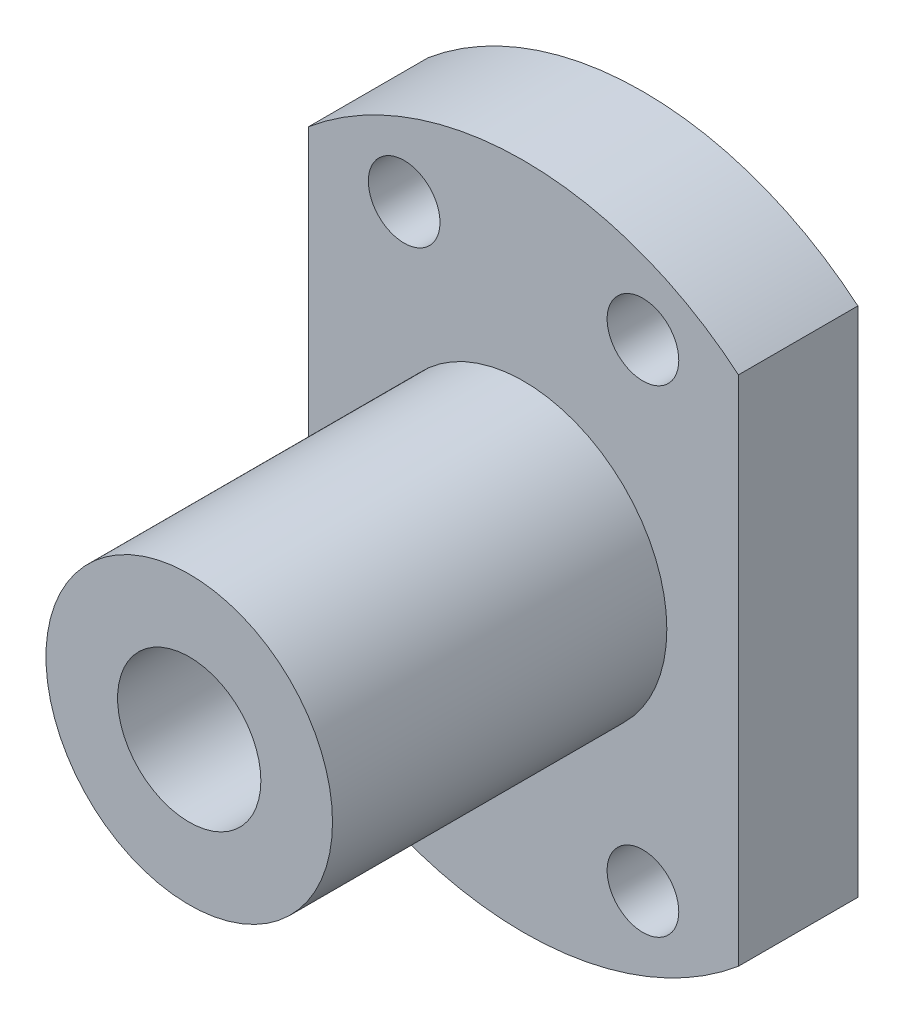
SolidWorks part; units mm, degrees
ref_plane "Front Plane" through (0, 0, 0) normal (0, 0, 1) x (1, 0, 0)
ref_plane "Top Plane" through (0, 0, 0) normal (0, 1, 0) x (1, 0, 0)
ref_plane "Right Plane" through (0, 0, 0) normal (1, 0, 0) x (0, 0, -1)
sketch "Sketch1" plane through (0, 0, 0) normal (0, 0, 1) x (1, 0, 0)
  line L0 (-9, 10.7238) -> (-9, -10.7238)
  line L1 (9, 10.7238) -> (9, -10.7238)
  line L2 (-9, 0) -> (9, 0) construction
  line L3 (-5, 10) -> (5, -10) construction
  line L4 (-5, -10) -> (5, 10) construction
  arc A0 (9, 10.7238) -> (-9, 10.7238) centre (0, 0) ccw
  arc A1 (-9, -10.7238) -> (9, -10.7238) centre (0, 0) ccw
  circle A2 centre (0, 0) radius 3
  circle A3 centre (-5, 10) radius 1.5
  circle A4 centre (5, 10) radius 1.5
  circle A5 centre (-5, -10) radius 1.5
  circle A6 centre (5, -10) radius 1.5
  point P7 (0, 0)
  point P18 (0, 0)
  point P19 (0, 0)
  dimension "D2" = 14
  dimension "D3" = 6
  dimension "D6" = 3
  dimension "D1" = 18
  dimension "D4" = 20
  dimension "D5" = 10
extrude "Boss-Extrude1" add sketch "Sketch1" along normal blind 5
sketch "Sketch2" plane through (0, 0, 5) normal (0, 0, 1) x (1, 0, 0)
  circle A0 centre (0, 0) radius 6
  circle A1 centre (0, 0) radius 3
  circle A2 centre (0, 0) radius 3 construction
  dimension "D1" = 12
extrude "Boss-Extrude2" add sketch "Sketch2" along normal blind 14
